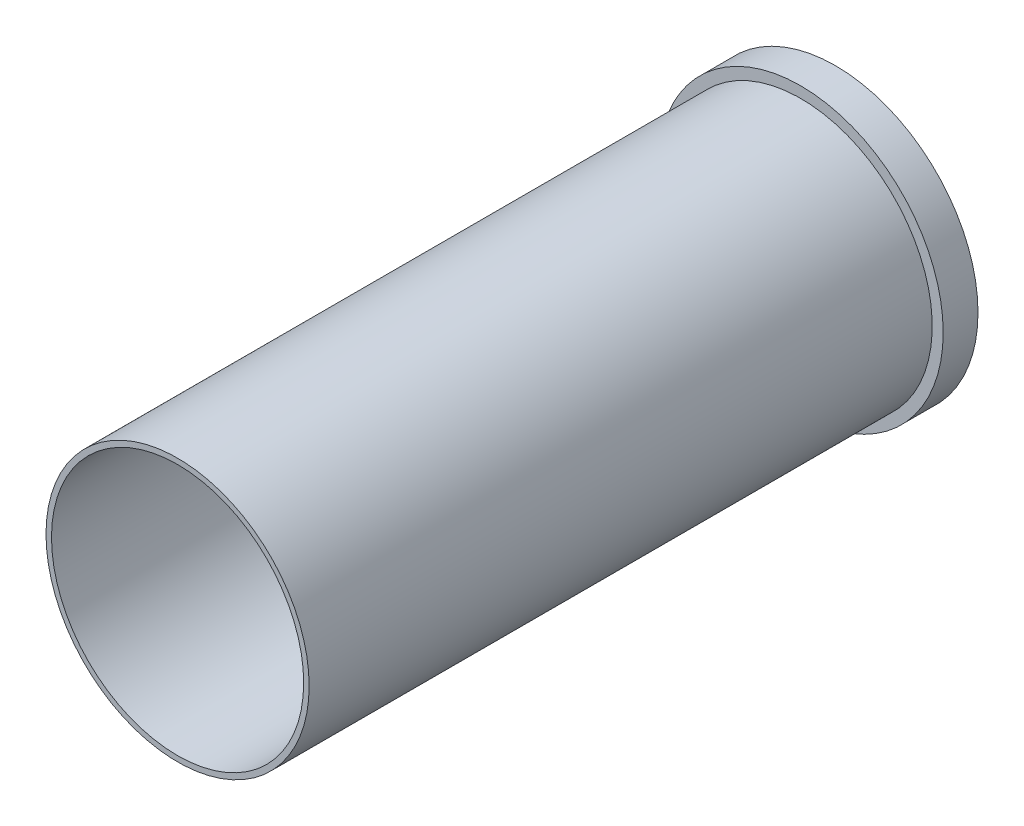
SolidWorks part; units mm, degrees
material "4032-T6"
ref_plane "Front Plane" through (0, 0, 0) normal (0, 0, 1) x (1, 0, 0)
ref_plane "Top Plane" through (0, 0, 0) normal (0, 1, 0) x (1, 0, 0)
ref_plane "Right Plane" through (0, 0, 0) normal (1, 0, 0) x (0, 0, -1)
ref_axis "Axis X" through (-88.99, 0, 0) along (1, 0, 0)
ref_axis "Axis Y" through (0, 55, 0) along (0, -1, 0)
ref_axis "Axis Z" through (0, 0, -88.99) along (0, 0, 1)
sketch "Sketch1" plane through (0, 0, 0) normal (0, 0, 1) x (1, 0, 0)
  circle A0 centre (0, 0) radius 23
  circle A1 centre (0, 0) radius 24
  dimension "D1" = 46
  dimension "D2" = 1
extrude "Boss-Extrude1" add sketch "Sketch1" along normal mid plane 120
sketch "Sketch2" plane through (0, 0, -60) normal (0, 0, -1) x (-1, 0, 0)
  circle A0 centre (0, 0) radius 24
  circle A1 centre (0, 0) radius 26
  circle A2 centre (0, 0) radius 24 construction
  dimension "D1" = 2
extrude "Boss-Extrude2" add sketch "Sketch2" against normal blind 6.35
